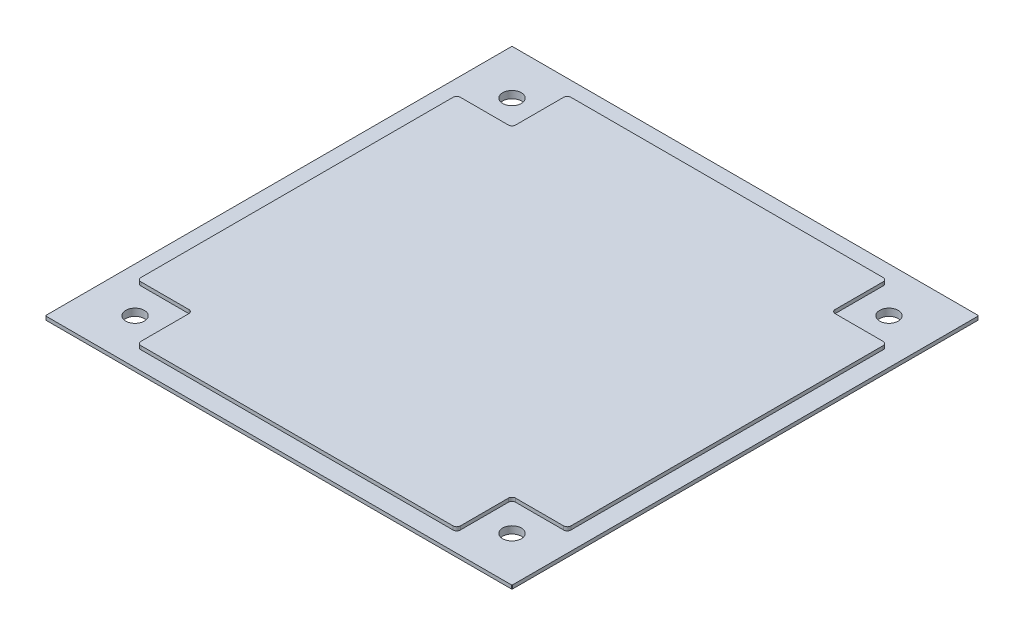
SolidWorks part; units mm, degrees
ref_plane "Front Plane" through (0, 0, 0) normal (0, 0, 1) x (1, 0, 0)
ref_plane "Top Plane" through (0, 0, 0) normal (0, 1, 0) x (1, 0, 0)
ref_plane "Right Plane" through (0, 0, 0) normal (1, 0, 0) x (0, 0, -1)
other "Configuration Table"
sketch "草图1" plane through (0, 0, 0) normal (0, 1, 0) x (1, 0, 0)
  line L1 (-65, 65) -> (65, 65)
  line L2 (-65, 65) -> (-65, -65)
  line L3 (-65, -65) -> (65, -65)
  line L4 (65, 65) -> (65, -65)
  line L5 (-65, 65) -> (65, -65) construction
  line L6 (-65, -65) -> (65, 65) construction
  point P0 (0, 0)
extrude "凸台-拉伸1" add sketch "草图1" along normal blind 3
sketch "草图2" plane through (0, 3, 0) normal (0, 1, 0) x (1, 0, 0)
  line L0 (52.5, 65) -> (52.5, 52.5) construction
  line L1 (65, 65) -> (-65, 65) construction
  line L2 (52.5, 52.5) -> (65, 52.5) construction
  line L3 (65, -65) -> (65, 65) construction
  line L4 (65, 52.5) -> (65, 65) construction
  line L5 (65, 65) -> (52.5, 65) construction
  circle A0 centre (52.5, 52.5) radius 2.6
  circle A1 centre (52.5, -52.5) radius 2.6
  circle A2 centre (-52.5, -52.5) radius 2.6
  circle A3 centre (-52.5, 52.5) radius 2.6
  point P19 (0, 0)
  dimension "D1" = 4
extrude "切除-拉伸1" cut sketch "草图2" against normal through all
sketch "草图4" plane through (0, 3, 0) normal (0, 1, 0) x (1, 0, 0)
  line L0 (65, 65) -> (44.5, 65)
  line L1 (44.5, 65) -> (44.5, 44.5)
  line L2 (44.5, 44.5) -> (65, 44.5)
  line L3 (65, -65) -> (65, 65) construction
  line L4 (65, 44.5) -> (65, 65)
  line L5 (65, -44.5) -> (44.5, -44.5)
  line L6 (44.5, -44.5) -> (44.5, -65)
  line L7 (44.5, -65) -> (65, -65)
  line L8 (65, -65) -> (65, -44.5)
  line L9 (-44.5, -65) -> (-44.5, -44.5)
  line L10 (-44.5, -44.5) -> (-65, -44.5)
  line L11 (-65, -44.5) -> (-65, -65)
  line L12 (-65, -65) -> (-44.5, -65)
  line L13 (-65, 44.5) -> (-44.5, 44.5)
  line L14 (-44.5, 44.5) -> (-44.5, 65)
  line L15 (-44.5, 65) -> (-65, 65)
  line L16 (-65, 65) -> (-65, 44.5)
  point P22 (0, 0)
  dimension "D1" = 4
extrude "切除-拉伸2" cut sketch "草图4" against normal blind 1
sketch "草图5" plane through (0, 3, 0) normal (0, 1, 0) x (1, 0, 0)
  line L5 (-44.5, 65) -> (44.5, 65)
  line L6 (44.5, 65) -> (44.5, 59.9)
  line L7 (44.5, 65) -> (44.5, 44.5) construction
  line L8 (-44.5, 65) -> (-44.5, 59.9)
  line L9 (-44.5, 44.5) -> (-44.5, 65) construction
  line L10 (-44.5, 59.9) -> (44.5, 59.9)
  line L11 (65, 44.5) -> (65, -44.5)
  line L12 (65, -44.5) -> (59.9, -44.5)
  line L13 (65, 44.5) -> (59.9, 44.5)
  line L14 (59.9, 44.5) -> (59.9, -44.5)
  line L15 (44.5, -65) -> (-44.5, -65)
  line L16 (-44.5, -65) -> (-44.5, -59.9)
  line L17 (44.5, -65) -> (44.5, -59.9)
  line L18 (44.5, -59.9) -> (-44.5, -59.9)
  line L19 (-65, -44.5) -> (-65, 44.5)
  line L20 (-65, 44.5) -> (-59.9, 44.5)
  line L21 (-65, -44.5) -> (-59.9, -44.5)
  line L22 (-59.9, -44.5) -> (-59.9, 44.5)
  point P27 (0, 0)
  dimension "D1" = 4
extrude "切除-拉伸3" cut sketch "草图5" against normal up to surface (1 mm away) up to face at (-54.75, 2, 54.75)
chamfer "倒角1" distance 0.2 angle 45 4 edges at (-65, 1, 65) (-65, 1, -65) (65, 1, -65) (65, 1, 65)
chamfer "倒角2" distance 1 angle 45 8 edges at (64.9, 0, 64.9) (65, 0, 0) (64.9, 0, -64.9) (0, 0, -65) (-64.9, 0, -64.9) (-65, 0, 0) (-64.9, 0, 64.9) (0, 0, 65)
fillet "圆角1" [suppressed] radius 0.5
fillet "圆角2" radius 1 12 edges at (44.5, 2.5, -59.9) (44.5, 2.5, -44.5) (59.9, 2.5, -44.5) (59.9, 2.5, 44.5) (44.5, 2.5, 44.5) (44.5, 2.5, 59.9) (-44.5, 2.5, 59.9) (-44.5, 2.5, 44.5) (-59.9, 2.5, 44.5) (-59.9, 2.5, -44.5) (-44.5, 2.5, -44.5) (-44.5, 2.5, -59.9)
